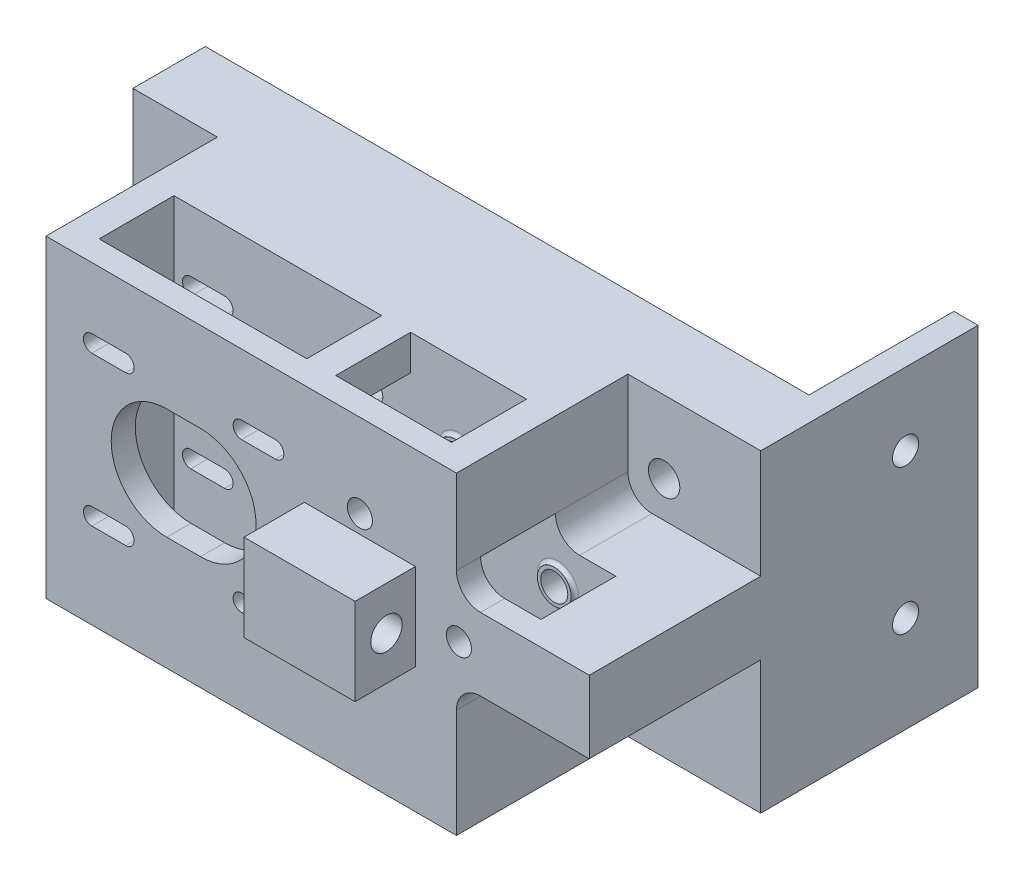
SolidWorks part; units mm, degrees
ref_plane "Front Plane" through (0, 0, 0) normal (0, 0, 1) x (1, 0, 0)
ref_plane "Top Plane" through (0, 0, 0) normal (0, 1, 0) x (1, 0, 0)
ref_plane "Right Plane" through (0, 0, 0) normal (1, 0, 0) x (0, 0, -1)
sketch "Sketch1" plane through (0, 0, 0) normal (0, 0, 1) x (1, 0, 0)
  line L0 (-62.5, 0) -> (-62.5, 30) construction
  line L1 (0, 0) -> (-125, 0)
  line L2 (0, 0) -> (0, 60)
  line L3 (0, 60) -> (-125, 60)
  line L4 (-125, 0) -> (-125, 60)
  line L5 (-15, 15) -> (-115, 15) construction
  line L6 (-15, 15) -> (-15, 45) construction
  line L7 (-15, 45) -> (-115, 45) construction
  line L8 (-115, 15) -> (-115, 45) construction
  line L11 (-62.5, 30) -> (0, 30) construction
  circle A0 centre (-42.5, 42.725) radius 2.8
  circle A1 centre (-22, 30) radius 2.8
  circle A2 centre (-15, 45) radius 3.25
  circle A3 centre (-15, 15) radius 3.25
  circle A4 centre (-115, 15) radius 2.75
  circle A5 centre (-115, 45) radius 2.75
  point P4 (-42.5, 42.725)
  point P8 (-22, 30)
  point P11 (-62.5, 30)
  dimension "D5" = 5.6
  dimension "D8" = 5.6
  dimension "D11" = 6.5
  dimension "D12" = 6.5
  dimension "D13" = 5.5
  dimension "D14" = 5.5
  dimension "D1" = 60
  dimension "D2" = 125
  dimension "D3" = 17.275
  dimension "D4" = 42.5
  dimension "D6" = 30
  dimension "D7" = 22
  dimension "D9" = 10
  dimension "D10" = 15
  dimension "D15" = 15
  dimension "D16" = 15
extrude "Boss-Extrude1" add sketch "Sketch1" along normal blind 30
sketch "Sketch2" plane through (0, 0, 30) normal (0, 0, 1) x (1, 0, 0)
  line L0 (-62.5, 60) -> (-62.5, 0) construction
  line L1 (0, 0) -> (-22.5, 0)
  line L2 (0, 0) -> (0, 22.5)
  line L3 (0, 22.5) -> (-17.5, 22.5)
  line L4 (-22.5, 0) -> (-22.5, 17.5)
  line L5 (0, 60) -> (-22.5, 60)
  line L6 (0, 60) -> (0, 37.5)
  line L7 (0, 37.5) -> (-17.5, 37.5)
  line L8 (-22.5, 60) -> (-22.5, 42.5)
  line L9 (0, 60) -> (-125, 60) construction
  line L10 (-125, 0) -> (0, 0) construction
  line L11 (-107.5, 60) -> (-107.5, 42.5)
  line L12 (-125, 37.5) -> (-112.5, 37.5)
  line L13 (-125, 60) -> (-125, 37.5)
  line L14 (-125, 60) -> (-107.5, 60)
  line L19 (-125, 60) -> (-125, 0) construction
  line L20 (-62.5, 30) -> (-125, 30) construction
  line L21 (-125, 0) -> (-107.5, 0)
  line L22 (-125, 0) -> (-125, 22.5)
  line L23 (-125, 22.5) -> (-112.5, 22.5)
  line L24 (-107.5, 0) -> (-107.5, 17.5)
  arc A0 (-17.5, 22.5) -> (-22.5, 17.5) centre (-17.5, 17.5) ccw
  arc A1 (-17.5, 37.5) -> (-22.5, 42.5) centre (-17.5, 42.5) cw
  arc A2 (-112.5, 37.5) -> (-107.5, 42.5) centre (-112.5, 42.5) ccw
  arc A4 (-112.5, 22.5) -> (-107.5, 17.5) centre (-112.5, 17.5) cw
  dimension "D5" = 5
  dimension "D7" = 5
  dimension "D1" = 22.5
  dimension "D2" = 22.5
  dimension "D3" = 22.5
  dimension "D4" = 22.5
  dimension "D6" = 17.5
extrude "Cut-Extrude1" cut sketch "Sketch2" against normal blind 15
sketch "Sketch3" plane through (0, 0, 0) normal (0, 0, -1) x (-1, 0, 0)
  circle A0 centre (22, 30) radius 3.25
  circle A1 centre (42.5, 42.725) radius 3.25
  dimension "D1" = 6.5
  dimension "D2" = 6.5
extrude "Cut-Extrude2" cut sketch "Sketch3" against normal blind 19
ref_plane "Plane1" through (0, 0, 45.5) normal (0, 0, 1) x (1, 0, 0)
sketch "Sketch4" plane through (0, 0, 45.5) normal (0, 0, 1) x (1, 0, 0)
  line L0 (-107.5, 60) -> (-107.5, 0)
  line L1 (-107.5, 0) -> (-22.5, 0)
  line L2 (-22.5, 17.5) -> (-22.5, 0) construction
  line L3 (-22.5, 0) -> (0, 0) construction
  line L4 (-22.5, 0) -> (-22.5, 17.5)
  line L5 (-22.5, 17.5) -> (-22.5, 0) construction
  line L6 (-107.5, 60) -> (-22.5, 60)
  line L7 (-22.5, 60) -> (-22.5, 42.5)
  line L8 (-17.5, 37.5) -> (0, 37.5)
  line L9 (0, 37.5) -> (0, 22.5)
  line L10 (0, 22.5) -> (-17.5, 22.5)
  arc A0 (-22.5, 17.5) -> (-17.5, 22.5) centre (-17.5, 17.5) cw
  arc A1 (-17.5, 37.5) -> (-22.5, 42.5) centre (-17.5, 42.5) cw
extrude "Boss-Extrude2" add sketch "Sketch4" along normal blind 5 separate body
sketch "Sketch5" plane through (0, 0, 30) normal (0, 0, 1) x (1, 0, 0)
  line L1 (-107.5, 0) -> (-101.5, 0)
  line L2 (-107.5, 0) -> (-107.5, 60)
  line L3 (-107.5, 60) -> (-101.5, 60)
  line L4 (-101.5, 0) -> (-101.5, 60)
  line L5 (-22.5, 0) -> (-28.5, 0)
  line L6 (-22.5, 0) -> (-22.5, 17.5)
  line L7 (-22.5, 17.5) -> (-28.5, 17.5)
  line L8 (-28.5, 0) -> (-28.5, 17.5)
  line L9 (-22.5, 60) -> (-28.5, 60)
  line L10 (-22.5, 60) -> (-22.5, 42.5)
  line L11 (-22.5, 42.5) -> (-28.5, 42.5)
  line L12 (-28.5, 60) -> (-28.5, 42.5)
  line L17 (-107.5, 42.5) -> (-107.5, 60) construction
  line L18 (-22.5, 60) -> (-107.5, 60) construction
  line L19 (-107.5, 0) -> (-22.5, 0) construction
  line L20 (-58.5, 60) -> (-52.5, 60)
  line L21 (-58.5, 60) -> (-58.5, 52.725)
  line L22 (-58.5, 52.725) -> (-52.5, 52.725)
  line L23 (-52.5, 60) -> (-52.5, 52.725)
  line L24 (-52.5, 0) -> (-55.5, 0)
  line L25 (-52.5, 0) -> (-52.5, 17.5)
  line L26 (-52.5, 17.5) -> (-55.5, 17.5)
  line L27 (-55.5, 0) -> (-55.5, 17.5)
  line L28 (-17.5, 37.5) -> (0, 37.5) construction
  line L29 (0, 22.5) -> (-10, 22.5)
  line L30 (0, 22.5) -> (0, 37.5)
  line L31 (0, 37.5) -> (-10, 37.5)
  line L32 (-10, 22.5) -> (-10, 37.5)
  circle A0 centre (-42.5, 42.725) radius 2.8 construction
  dimension "D1" = 6
  dimension "D2" = 10
  dimension "D3" = 6
  dimension "D4" = 17.5
  dimension "D5" = 17.5
  dimension "D6" = 10
  dimension "D7" = 10
  dimension "D8" = 6
  dimension "D9" = 3
extrude "Boss-Extrude3" add sketch "Sketch5" along normal up to next
sketch "Sketch6" plane through (0, 0, 50.5) normal (0, 0, 1) x (1, 0, 0)
  line L0 (-82.5, 30) -> (-75.5, 30) construction
  line L1 (-82.5, 41.5) -> (-75.5, 41.5)
  line L2 (-82.5, 18.5) -> (-75.5, 18.5)
  line L3 (-75.5, 30) -> (0, 30) construction
  line L4 (0, 22.5) -> (0, 37.5) construction
  line L5 (-91, 45.5) -> (-98, 45.5) construction
  line L6 (-91, 43.75) -> (-98, 43.75)
  line L7 (-91, 47.25) -> (-98, 47.25)
  line L8 (-67, 45.5) -> (-60, 45.5) construction
  line L9 (-67, 47.25) -> (-60, 47.25)
  line L10 (-67, 43.75) -> (-60, 43.75)
  line L11 (-91, 14.5) -> (-98, 14.5) construction
  line L12 (-91, 12.75) -> (-98, 12.75)
  line L13 (-91, 16.25) -> (-98, 16.25)
  line L14 (-67, 14.5) -> (-60, 14.5) construction
  line L15 (-67, 16.25) -> (-60, 16.25)
  line L16 (-67, 12.75) -> (-60, 12.75)
  line L17 (-94.5, 14.5) -> (-94.5, 45.5) construction
  line L18 (-63.5, 45.5) -> (-63.5, 14.5) construction
  arc A0 (-82.5, 41.5) -> (-82.5, 18.5) centre (-82.5, 30) ccw
  arc A1 (-75.5, 18.5) -> (-75.5, 41.5) centre (-75.5, 30) ccw
  arc A2 (-91, 43.75) -> (-91, 47.25) centre (-91, 45.5) ccw
  arc A3 (-98, 47.25) -> (-98, 43.75) centre (-98, 45.5) ccw
  arc A4 (-67, 47.25) -> (-67, 43.75) centre (-67, 45.5) ccw
  arc A5 (-60, 43.75) -> (-60, 47.25) centre (-60, 45.5) ccw
  arc A6 (-91, 12.75) -> (-91, 16.25) centre (-91, 14.5) ccw
  arc A7 (-98, 16.25) -> (-98, 12.75) centre (-98, 14.5) ccw
  arc A8 (-67, 16.25) -> (-67, 12.75) centre (-67, 14.5) ccw
  arc A9 (-60, 12.75) -> (-60, 16.25) centre (-60, 14.5) ccw
  point P2 (-79, 30)
  point P12 (-94.5, 45.5)
  point P19 (-63.5, 45.5)
  point P26 (-94.5, 14.5)
  point P33 (-63.5, 14.5)
  dimension "D8" = 1.75
  dimension "D11" = 1.75
  dimension "D12" = 1.75
  dimension "D15" = 1.75
  dimension "D1" = 7
  dimension "D2" = 23
  dimension "D3" = 75.5
  dimension "D4" = 15.5
  dimension "D5" = 15.5
  dimension "D6" = 15.5
  dimension "D7" = 15.5
  dimension "D9" = 7
  dimension "D10" = 7
  dimension "D13" = 7
  dimension "D14" = 7
extrude "Cut-Extrude3" cut sketch "Sketch6" against normal through all
sketch "Sketch7" plane through (0, 0, 50.5) normal (0, 0, 1) x (1, 0, 0)
  line L1 (-54, 39) -> (-31, 39)
  line L2 (-54, 39) -> (-54, 21)
  line L3 (-54, 21) -> (-31, 21)
  line L4 (-31, 39) -> (-31, 21)
  arc A0 (-82.5, 41.5) -> (-82.5, 18.5) centre (-82.5, 30) ccw construction
  dimension "D1" = 21.5
  dimension "D2" = 18
  dimension "D3" = 9
  dimension "D4" = 23
extrude "Boss-Extrude4" add sketch "Sketch7" along normal blind 12.5
sketch "Sketch8" plane through (-31, 0, 0) normal (1, 0, 0) x (0, 0, -1)
  line L0 (-50.5, 21) -> (-50.5, 39) construction
  line L1 (-63, 39) -> (-50.5, 39) construction
  circle A0 centre (-56.5, 30) radius 3.25
  dimension "D1" = 6.5
  dimension "D2" = 6
  dimension "D3" = 9
extrude "Cut-Extrude4" cut sketch "Sketch8" against normal through all
sketch "Sketch9" plane through (0, 0, 0) normal (0, -1, 0) x (1, 0, 0)
  line L0 (-125, 15) -> (-107.5, 15)
  line L1 (-107.5, 15) -> (-107.5, 50.5)
  line L2 (-107.5, 15) -> (-107.5, 50.5) construction
  line L3 (-107.5, 50.5) -> (-22.5, 50.5)
  line L4 (-22.5, 50.5) -> (-22.5, 15)
  line L5 (-22.5, 15) -> (0, 15)
  line L6 (0, 15) -> (0, -30)
  line L7 (0, -30) -> (-125, -30)
  line L8 (-125, -30) -> (-125, 15)
  line L9 (-125, 0) -> (0, 0) construction
  line L10 (-52.5, 45.5) -> (-28.5, 45.5)
  line L11 (-52.5, 45.5) -> (-52.5, 30)
  line L12 (-52.5, 30) -> (-28.5, 30)
  line L13 (-28.5, 45.5) -> (-28.5, 30)
  line L14 (-55.5, 45.5) -> (-101.5, 45.5)
  line L15 (-55.5, 45.5) -> (-55.5, 30)
  line L16 (-55.5, 30) -> (-101.5, 30)
  line L17 (-101.5, 45.5) -> (-101.5, 30)
  line L18 (-125, -15) -> (0, -15) construction
  circle A0 centre (-110, -15) radius 2.7
  circle A1 centre (-80, -15) radius 2.7
  circle A2 centre (-45, -15) radius 2.7
  circle A3 centre (-15, -15) radius 2.7
  dimension "D3" = 15
  dimension "D4" = 30
  dimension "D5" = 15
  dimension "D6" = 30
  dimension "D7" = 5.4
  dimension "D8" = 5.4
  dimension "D9" = 5.4
  dimension "D10" = 5.4
  dimension "D1" = 30
  dimension "D2" = 15
extrude "Boss-Extrude5" add sketch "Sketch9" along normal blind 5
sketch "Sketch10" plane through (0, 0, 0) normal (1, 0, 0) x (0, 0, -1)
  line L0 (-50.5, 37.5) -> (-50.5, 22.5)
  line L1 (-50.5, 22.5) -> (-15, 22.5)
  line L2 (-15, 22.5) -> (-15, -5)
  line L3 (-15, -5) -> (30, -5)
  line L4 (30, -5) -> (30, 60)
  line L5 (-50.5, 37.5) -> (-15, 37.5)
  line L6 (-15, 37.5) -> (-15, 60)
  line L7 (-15, 60) -> (30, 60)
  line L8 (15, 0) -> (15, 60) construction
  line L9 (30, 0) -> (0, 0) construction
  circle A0 centre (15, 45) radius 2.7
  circle A1 centre (15, 15) radius 2.7
  dimension "D1" = 15
  dimension "D2" = 30
  dimension "D3" = 5.4
  dimension "D4" = 5.4
extrude "Boss-Extrude6" add sketch "Sketch10" along normal blind 5
sketch "Sketch11" plane through (0, 0, 45.5) normal (0, 0, -1) x (-1, 0, 0)
  circle A0 centre (42.5, 42.725) radius 2.6
  circle A1 centre (22, 30) radius 2.6
  dimension "D1" = 5.2
  dimension "D2" = 5.2
extrude "Cut-Extrude5" cut sketch "Sketch11" against normal through all
sketch "Sketch12" plane through (0, 0, 30) normal (0, 0, 1) x (1, 0, 0)
  circle A0 centre (-42.5, 42.725) radius 2.8
  circle A1 centre (-22, 30) radius 2.8
  circle A2 centre (-22, 30) radius 3.5
  circle A3 centre (-42.5, 42.725) radius 3.5
  circle A4 centre (-42.5, 42.725) radius 2.8 construction
  circle A5 centre (-22, 30) radius 2.8 construction
  dimension "D1" = 7
  dimension "D2" = 7
extrude "Boss-Extrude7" add sketch "Sketch12" along normal blind 0.75
fillet "Fillet1" radius 0.75 2 edges at (-39, 42.725, 30) (-18.5, 30, 30)
